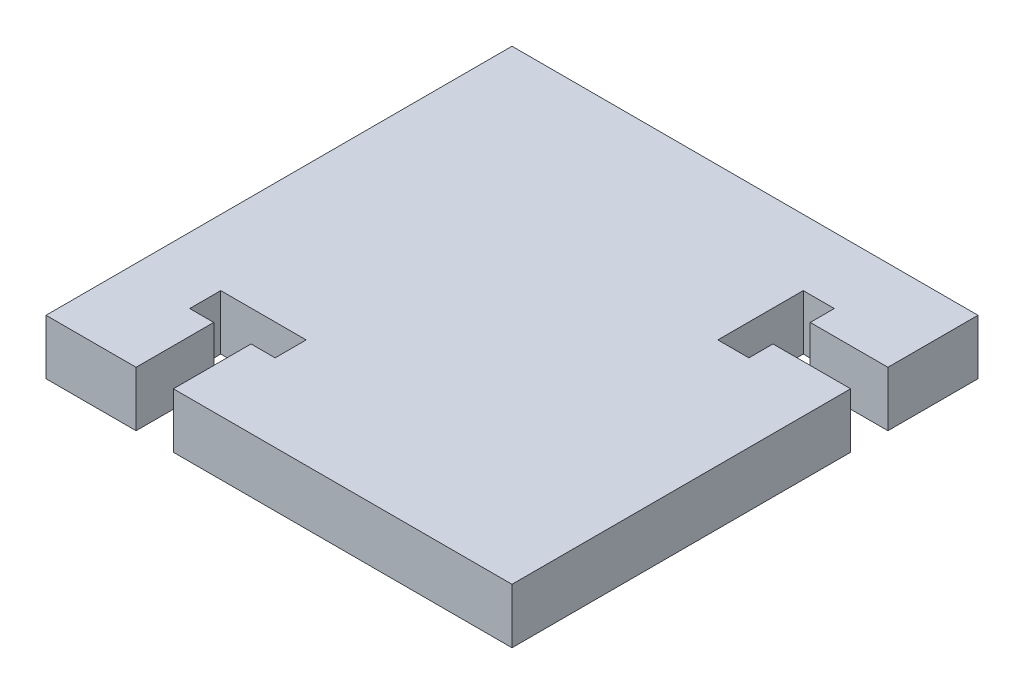
SolidWorks part; units mm, degrees
ref_plane "Front Plane" through (0, 0, 0) normal (0, 0, 1) x (1, 0, 0)
ref_plane "Top Plane" through (0, 0, 0) normal (0, 1, 0) x (1, 0, 0)
ref_plane "Right Plane" through (0, 0, 0) normal (1, 0, 0) x (0, 0, -1)
sketch "Sketch1" plane through (0, 0, 0) normal (0, 1, 0) x (1, 0, 0)
  line L0 (-30.734, 0) -> (-30.734, 6.35)
  line L1 (-38.1, 38.1) -> (0, 38.1)
  line L2 (-38.1, 38.1) -> (-38.1, 0)
  line L3 (-38.1, 0) -> (-30.734, 0)
  line L4 (0, 38.1) -> (0, 30.734)
  line L5 (-30.734, 6.35) -> (-32.7025, 6.35)
  line L6 (-32.7025, 6.35) -> (-32.7025, 8.89)
  line L7 (-32.7025, 8.89) -> (-25.7175, 8.89)
  line L8 (-25.7175, 8.89) -> (-25.7175, 6.35)
  line L9 (-25.7175, 6.35) -> (-27.686, 6.35)
  line L10 (-27.686, 6.35) -> (-27.686, 0)
  line L11 (-29.21, 8.89) -> (-29.21, 0) construction
  line L12 (-30.734, 6.35) -> (-27.686, 6.35) construction
  line L13 (-29.21, 8.89) -> (-29.21, 29.21) construction
  line L14 (-29.21, 29.21) -> (0, 29.21) construction
  line L15 (-38.1, 29.21) -> (-29.21, 29.21) construction
  line L16 (-29.21, 29.21) -> (-29.21, 38.1) construction
  line L17 (-8.89, 25.7175) -> (-8.89, 32.7025)
  line L18 (-8.89, 32.7025) -> (-6.35, 32.7025)
  line L19 (-6.35, 25.7175) -> (-8.89, 25.7175)
  line L20 (-6.35, 27.686) -> (-6.35, 25.7175)
  line L21 (0, 27.686) -> (-6.35, 27.686)
  line L22 (-6.35, 30.734) -> (0, 30.734)
  line L23 (-6.35, 32.7025) -> (-6.35, 30.734)
  line L24 (0, 30.734) -> (0, 27.686) construction
  line L25 (-25.7175, 8.89) -> (-29.21, 29.21) construction
  line L26 (-27.686, 0) -> (0, 0)
  line L27 (0, 27.686) -> (0, 0)
  line L28 (-29.21, 29.21) -> (-8.89, 25.7175) construction
  line L29 (-6.35, 30.734) -> (-6.35, 27.686) construction
  point P4 (-6.4353, 26.1525)
  point P17 (-29.21, 6.35)
  point P27 (0, 29.21)
  point P31 (-28.9696, 28.9696)
  dimension "D1" = 38.1
  dimension "D2" = 38.1
  dimension "D3" = 3.048
  dimension "D4" = 8.89
  dimension "D5" = 2.54
  dimension "D6" = 8.89
  dimension "D7" = 6.985
extrude "Boss-Extrude1" add sketch "Sketch1" along normal blind 4.4958
